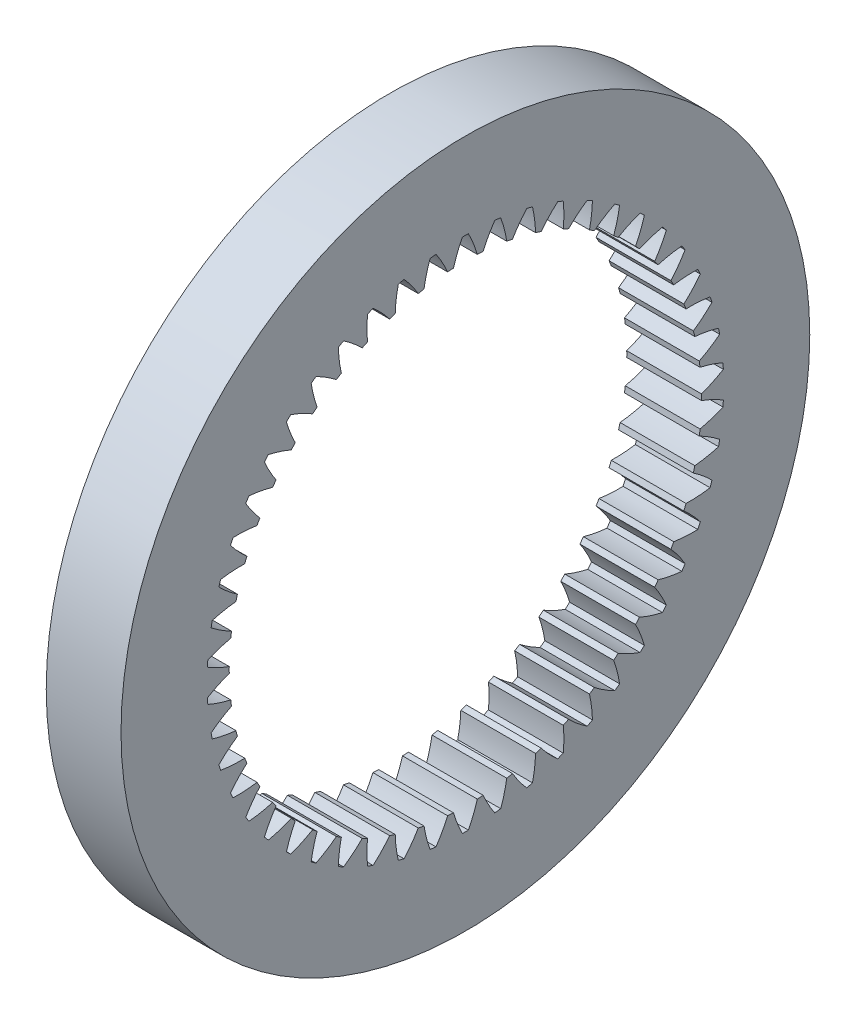
SolidWorks part; units mm, degrees
ref_plane "Plane1" through (0, 0, 0) normal (0, 0, 1) x (1, 0, 0)
ref_plane "Plane2" through (0, 0, 0) normal (0, 1, 0) x (1, 0, 0)
ref_plane "Plane3" through (0, 0, 0) normal (1, 0, 0) x (0, 0, -1)
other "Configuration Table"
sketch "HoldingSke" plane through (0, 0, 0) normal (0, 1, 0) x (1, 0, 0)
  line L0 (0, 0) -> (0.3214, -0.383)
  line L1 (-15, 0) -> (100, 0) construction
  line L2 (0, 0) -> (-2.1039, 2.3779)
  line L3 (0, 0) -> (-11.863, 4.5341)
  line L4 (0, 0) -> (5.5511, 6.6156)
  line L5 (0, 0) -> (-23.7986, -8.8762)
  line L6 (0, 0) -> (-10.5278, -7.1032)
  line L7 (-2.1039, 2.3779) -> (3.3635, 27.1825)
  line L8 (-76.2, 4.3779) -> (-54.61, 4.3779)
  line L9 (-71.009, 38.7566) -> (-53.1078, 45.2721)
  line L10 (-76.2, 71.12) -> (104.1128, 71.12)
  line L11 (0, 0) -> (-15.2, 0)
  line L12 (-76.2, 101.6) -> (-76.133, 101.6)
  line L13 (24.9733, 27.94) -> (52.9518, 28.4284)
  line L14 (24.9733, 27.94) -> (24.9743, 27.94)
  line L15 (24.9733, 27.94) -> (100.4006, 29.5858)
  circle A0 centre (0, 0) radius 70
  circle A1 centre (0, 0) radius 12.7
  circle A2 centre (0, 0) radius 12.7
  dimension "Num_teeth" = 50
  dimension "Pitch_radius" = 180.3128
  dimension "Width" = 15.2
  dimension "Diameter" = 140
sketch "BasProSke" plane through (0, 0, 0) normal (0, 1, 0) x (1, 0, 0)
  line L0 (-10, 0) -> (60, 0) construction
  line L1 (0, 48) -> (0, 70)
  line L2 (0, 48) -> (15.2, 48)
  line L3 (15.2, 48) -> (15.2, 70)
  line L4 (15.2, 70) -> (0, 70)
  dimension "Thickness" = 15.2
  dimension "Diameter" = 140
revolve "Base-Revolve" add sketch "BasProSke" angle 360 about L0
sketch "TooCutSke" plane through (0, 0, 0) normal (1, 0, 0) x (0, 0, -1)
  line L3 (1.738, 49.9698) -> (1.738, 53.6633) construction
  line L4 (0, 0) -> (0, 59.563) construction
  line L5 (0, 0) -> (-4.2903, 68.1927) construction
  line L6 (-21.6015, 41.0107) -> (35.113, 44.5789) construction
  circle A0 centre (0, 0) radius 50 construction
  circle A1 centre (0, 0) radius 52.501 construction
  circle A2 centre (0, 0) radius 42.2862 construction
  circle A3 centre (0, 0) radius 47.9746 construction
  arc A4 (2.4267, 47.9132) -> (0.6033, 52.4975) centre (-21.6015, 41.0107) ccw
  arc A5 (2.4267, 47.9132) -> (-2.4267, 47.9132) centre (0, 0) ccw
  arc A6 (0.6033, 52.4975) -> (-0.6033, 52.4975) centre (0, 0) ccw
  arc A7 (-0.6033, 52.4975) -> (-2.4267, 47.9132) centre (21.6015, 41.0107) ccw
extrude "ToothCut" cut sketch "TooCutSke" along normal through all
fillet "Breaks" [suppressed] radius 0.2
fillet "RootFillets" [suppressed] radius 0.501
pattern_circular "TeethCuts" count 50 every 7.2 about axis through (-10, 0, 0) along (1, 0, 0) of "RootFillets", "Breaks", "ToothCut"
equation "' \"Module@HoldingSke\" = 6.35"
equation "' \"Num_teeth@HoldingSke\" = 24"
equation "' \"Ap@HoldingSke\" =  14.5"
equation "' \"Ap@HoldingSke\" = 14.5"
equation "' \"Width@HoldingSke\" = 12"
equation "' \"Diameter@HoldingSke\" = 8 * 25.4"
equation "' \"Show_teeth@HoldingSke\" = 100"
equation "' \"Backlash@HoldingSke\" = 0.009 * 25.4"
equation "' \"Addendum_fac@HoldingSke\" = 1.0"
equation "' \"Dedendum_fac@HoldingSke\" = 1.25"
equation "' \"Dedendum_add@HoldingSke\" = 0.00005 * 25.4"
equation "' \"Clearance_fac@HoldingSke\" = 0.25"
equation "\"Pitch@HoldingSke\" = 1 / \"Module@HoldingSke\" "
equation "\"Overcut_dia@TooCutSke\" = (\"Num_teeth@HoldingSke\" - 2 * \"Addendum_fac@HoldingSke\") / \"Pitch@HoldingSke\" - 0.002 * 25.4"
equation "\"Pitch_dia@TooCutSke\" = \"Num_teeth@HoldingSke\" / \"Pitch@HoldingSke\""
equation "\"Base_dia@TooCutSke\" = \"Num_teeth@HoldingSke\" / \"Pitch@HoldingSke\" * cos((\"Ap@HoldingSke\"  * 3.14159265 / 180)) * 0.90"
equation "\"Root_dia@TooCutSke\" = \"Num_teeth@HoldingSke\"  / \"Pitch@HoldingSke\" + 2 *  \"Dedendum_fac@HoldingSke\"/ \"Pitch@HoldingSke\" + \"Dedendum_add@HoldingSke\" * 2"
equation "\"Half_ang@TooCutSke\" = 180 / \"Num_teeth@HoldingSke\""
equation "\"Half_CT@TooCutSke\" = \"Num_teeth@HoldingSke\" / \"Pitch@HoldingSke\" * sin((3.14159265 / 2 / \"Num_teeth@HoldingSke\")) / 2 + 10 * \"Backlash@HoldingSke\" / 4"
equation "\"Flank_rad@TooCutSke\" = \"Num_teeth@HoldingSke\" / \"Pitch@HoldingSke\" / 4"
equation "\"Radius@RootFillets\"= \"Clearance_fac@HoldingSke\" / \"Pitch@HoldingSke\" + \"Dedendum_add@HoldingSke\""
equation "\"Break_rad@Breaks\" = 0.02 / \"Pitch@HoldingSke\" * 5"
equation "\"Num_teeth@TeethCuts\" = int( \"Show_teeth@HoldingSke\" ) + 1"
equation "\"Num_teeth@TeethCuts\" = ((sgn( \"Num_teeth@TeethCuts\" - \"Num_teeth@HoldingSke\" )-1)*( \"Num_teeth@TeethCuts\" - \"Num_teeth@HoldingSke\" ))/-2+ \"Num_teeth@HoldingSke\""
equation "\"Num_teeth@TeethCuts\" = ((sgn( \"Num_teeth@TeethCuts\" - 2.0)+1)*( \"Num_teeth@TeethCuts\" - 2.0))/2 +2.0"
equation "\"Angle@TeethCuts\" = 360.0 / \"Num_teeth@HoldingSke\""
equation "\"Diameter@BasProSke\" = \"Num_teeth@HoldingSke\"  / \"Pitch@HoldingSke\" + 2 *  \"Dedendum_fac@HoldingSke\"/ \"Pitch@HoldingSke\" + \"Dedendum_add@HoldingSke\" * 2 + 0.002 * 25.4"
equation "\"Diameter@BasProSke\" = ((sgn( \"Diameter@BasProSke\"  - \"Diameter@HoldingSke\" )+1)*( \"Diameter@BasProSke\"  - \"Diameter@HoldingSke\" ))/2 + \"Diameter@HoldingSke\""
equation "\"Inside_diameter@BasProSke\" =  (\"Num_teeth@HoldingSke\" - 2 * \"Addendum_fac@HoldingSke\") / \"Pitch@HoldingSke\" "
equation "\"Thickness@BasProSke\"  = \"Width@HoldingSke\""
